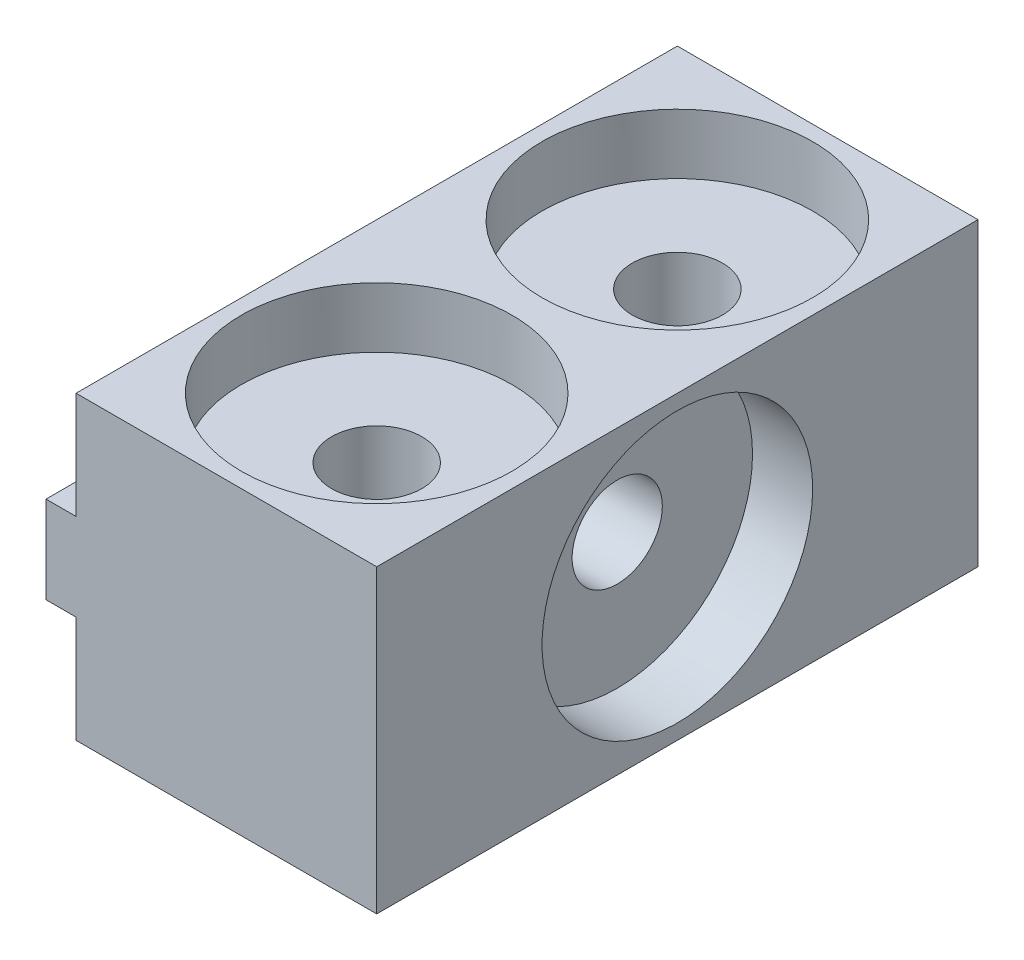
SolidWorks part; units mm, degrees
ref_plane "Front Plane" through (0, 0, 0) normal (0, 0, 1) x (1, 0, 0)
ref_plane "Top Plane" through (0, 0, 0) normal (0, 1, 0) x (1, 0, 0)
ref_plane "Right Plane" through (0, 0, 0) normal (1, 0, 0) x (0, 0, -1)
sketch "Sketch1" plane through (0, 0, 0) normal (0, 0, 1) x (1, 0, 0)
  line L0 (-10, 0) -> (-10, -3.55)
  line L1 (-10, -3.55) -> (-11, -3.55)
  line L2 (-11, -3.55) -> (-11, -6.45)
  line L3 (-11, -6.45) -> (-10, -6.45)
  line L4 (-10, -6.45) -> (-10, -10)
  line L5 (-10, -10) -> (0, -10)
  line L8 (0, -10) -> (0, 0)
  line L9 (0, 0) -> (-10, 0)
  dimension "D1" = 10
  dimension "D2" = 1
  dimension "D3" = 2.9
  dimension "D4" = 10
extrude "Boss-Extrude1" add sketch "Sketch1" along normal blind 20
sketch "Sketch2" plane through (0, 0, 0) normal (0, 1, 0) x (1, 0, 0)
  line L1 (-10, -20) -> (-10, 0) construction
  line L2 (0, -20) -> (-10, -20) construction
  circle A0 centre (-5, -15) radius 1.5
  dimension "D1" = 3
  dimension "D2" = 5
  dimension "D3" = 5
extrude "Cut-Extrude1" cut sketch "Sketch2" against normal through all
sketch "Sketch3" plane through (0, 0, 0) normal (1, 0, 0) x (0, 0, -1)
  line L0 (-20, -10) -> (-20, 0) construction
  circle A0 centre (-10, -5) radius 4.5
  dimension "D1" = 9
  dimension "D2" = 10
  dimension "D3" = 5
extrude "Cut-Extrude2" cut sketch "Sketch3" against normal blind 2
sketch "Sketch4" plane through (-2, 0, 0) normal (1, 0, 0) x (0, 0, -1)
  circle A0 centre (-10, -5) radius 1.5
  circle A1 centre (-10, -5) radius 4.5 construction
  dimension "D1" = 3
extrude "Cut-Extrude3" cut sketch "Sketch4" against normal through all
sketch "Sketch6" plane through (0, 0, 0) normal (0, 1, 0) x (1, 0, 0)
  circle A0 centre (-5, -15) radius 4.5
  circle A1 centre (-5, -15) radius 1.5 construction
  dimension "D1" = 9
extrude "Cut-Extrude4" cut sketch "Sketch6" against normal blind 2
pattern_linear "LPattern1" count 2 spacing 10 along (0, 0, -1) of "Cut-Extrude1", "Cut-Extrude4"
